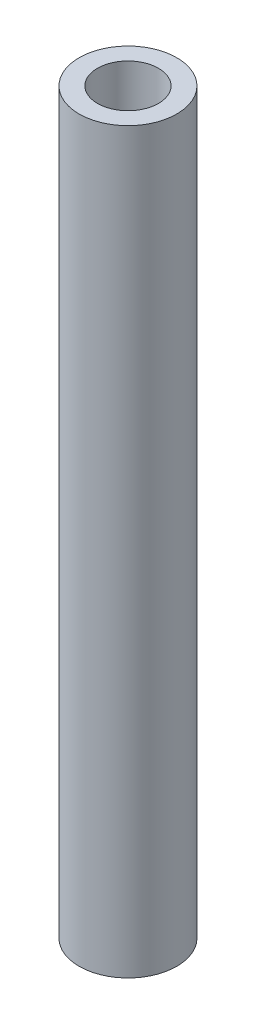
SolidWorks part; units mm, degrees
ref_plane "Front Plane" through (0, 0, 0) normal (0, 0, 1) x (1, 0, 0)
ref_plane "Top Plane" through (0, 0, 0) normal (0, 1, 0) x (1, 0, 0)
ref_plane "Right Plane" through (0, 0, 0) normal (1, 0, 0) x (0, 0, -1)
sketch "Szkic1" plane through (0, 0, 0) normal (0, 1, 0) x (1, 0, 0)
  circle A0 centre (-3.4437, 0) radius 2.5
  circle A1 centre (-3.4437, 0) radius 4
  dimension "D1" = 5
  dimension "D2" = 8
extrude "Dodanie-wyciągnięcie1" add sketch "Szkic1" along normal blind 60.5
